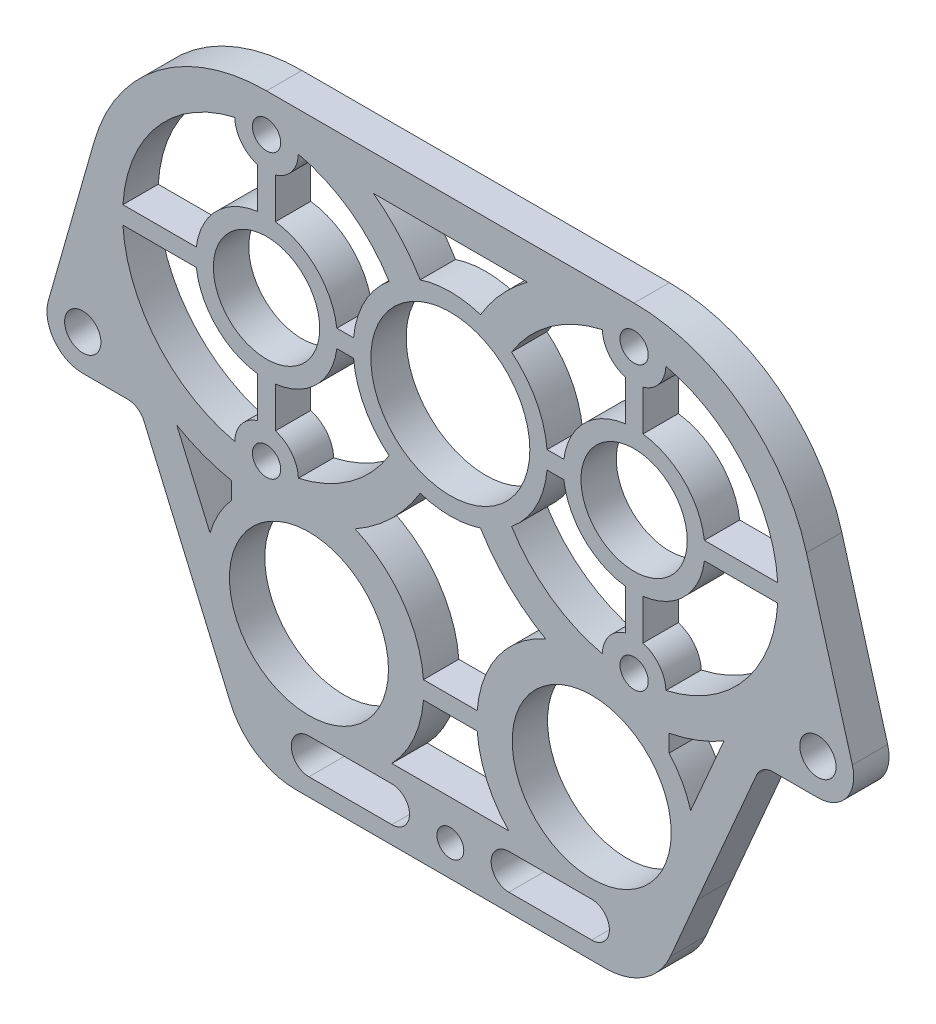
SolidWorks part; units mm, degrees
material "6061 Alloy"
ref_plane "Front Plane" through (0, 0, 0) normal (0, 0, 1) x (1, 0, 0)
ref_plane "Top Plane" through (0, 0, 0) normal (0, 1, 0) x (1, 0, 0)
ref_plane "Right Plane" through (0, 0, 0) normal (1, 0, 0) x (0, 0, -1)
sketch "Sketch1" plane through (0, 0, 0) normal (0, 0, 1) x (1, 0, 0)
  line L0 (-88.7296, -57.0475) -> (-96.9696, -85.9369)
  line L1 (-70.3836, -64.2939) -> (-83.566, -64.2939)
  line L2 (-59.3451, -45.9715) -> (-59.3451, -53.2554)
  line L3 (-59.3451, -85.7913) -> (-59.3451, -78.5074)
  line L4 (-56.1701, -45.9715) -> (-56.1701, -53.2554)
  line L5 (-45.1316, -64.2939) -> (-42.1278, -64.2939)
  line L6 (-56.1701, -85.7913) -> (-56.1701, -78.5074)
  line L7 (-70.3836, -67.4689) -> (-83.566, -67.4689)
  line L8 (-73.8894, -93.7574) -> (-67.9201, -107.5525)
  line L9 (-45.1316, -67.4689) -> (-42.1278, -67.4689)
  line L10 (-64.0572, -97.4665) -> (-64.0572, -100.5443)
  line L11 (-69.0893, -120.875) -> (-60.9774, -139.773)
  line L13 (-29.5612, -111.198) -> (-19.9139, -111.198)
  line L14 (-14.2297, -127.073) -> (-35.2455, -127.073)
  line L15 (-29.5612, -114.373) -> (-19.9139, -114.373)
  line L16 (-57.7576, -33.6742) -> (8.2824, -33.6742)
  line L17 (-10.9194, -40.0242) -> (-38.5558, -40.0242)
  line L18 (30.2994, -96.0869) -> (19.6141, -120.875)
  line L19 (-4.3436, -67.4689) -> (-7.3474, -67.4689)
  line L20 (41.3024, -94.1419) -> (33.2559, -94.1419)
  line L21 (20.9084, -67.4689) -> (34.0908, -67.4689)
  line L22 (6.6949, -85.7913) -> (6.6949, -78.5074)
  line L23 (-4.3436, -64.2939) -> (-7.3474, -64.2939)
  line L24 (6.6949, -45.9715) -> (6.6949, -53.2554)
  line L25 (9.8699, -85.7913) -> (9.8699, -78.5074)
  line L26 (9.8699, -45.9715) -> (9.8699, -53.2554)
  line L27 (20.9084, -64.2939) -> (34.0908, -64.2939)
  line L28 (39.2544, -57.0475) -> (47.4944, -85.9369)
  line L29 (-90.7776, -94.1419) -> (-82.7311, -94.1419)
  line L30 (-79.7746, -96.0869) -> (-69.0893, -120.875)
  line L31 (-60.9774, -139.773) -> (11.5022, -139.773)
  line L32 (19.6141, -120.875) -> (11.5022, -139.773)
  line L33 (24.4142, -93.7574) -> (18.4449, -107.5525)
  line L34 (-35.2455, -133.423) -> (-50.1376, -133.423) construction
  line L35 (-35.2455, -136.598) -> (-50.1376, -136.598)
  line L36 (-35.2455, -130.248) -> (-50.1376, -130.248)
  line L37 (0.6624, -133.423) -> (-14.2297, -133.423) construction
  line L38 (0.6624, -136.598) -> (-14.2297, -136.598)
  line L39 (0.6624, -130.248) -> (-14.2297, -130.248)
  line L40 (14.582, -97.4665) -> (14.582, -100.5443)
  circle A0 centre (-57.7576, -65.8814) radius 9.5504
  circle A1 centre (-57.7576, -40.4814) radius 2.54
  arc A2 (-41.8493, -93.8855) -> (-30.1579, -82.4814) centre (-57.7576, -65.8814) ccw
  circle A3 centre (-57.7576, -91.2814) radius 2.54
  circle A4 centre (-90.7776, -87.703) radius 3.2639
  arc A5 (-52.0455, -91.0998) -> (-56.1701, -85.7913) centre (-57.7576, -91.2814) ccw
  arc A6 (-52.0455, -91.0998) -> (-35.741, -79.4411) centre (-57.7576, -65.8814) ccw
  arc A7 (-52.0455, -40.663) -> (-56.1701, -45.9715) centre (-57.7576, -40.4814) cw
  arc A8 (-59.3451, -45.9715) -> (-63.4697, -40.663) centre (-57.7576, -40.4814) cw
  arc A9 (-56.1701, -78.5074) -> (-45.1316, -67.4689) centre (-57.7576, -65.8814) ccw
  arc A10 (-59.3451, -85.7913) -> (-63.4697, -91.0998) centre (-57.7576, -91.2814) ccw
  arc A11 (-83.566, -67.4689) -> (-63.4697, -91.0998) centre (-57.7576, -65.8814) ccw
  arc A12 (-59.3451, -53.2554) -> (-70.3836, -64.2939) centre (-57.7576, -65.8814) ccw
  circle A13 centre (-50.1376, -112.7855) radius 14.2875
  arc A14 (-70.3836, -67.4689) -> (-59.3451, -78.5074) centre (-57.7576, -65.8814) ccw
  arc A15 (-45.1316, -64.2939) -> (-56.1701, -53.2554) centre (-57.7576, -65.8814) ccw
  arc A16 (-63.4697, -40.663) -> (-83.566, -64.2939) centre (-57.7576, -65.8814) ccw
  arc A17 (-30.1579, -82.4814) -> (-19.3173, -82.4814) centre (-24.7376, -65.8814) ccw
  arc A18 (-64.0572, -100.5443) -> (-67.9201, -107.5525) centre (-50.1376, -112.7855) ccw
  arc A19 (39.1749, -56.7733) -> (39.2544, -57.0475) centre (8.2824, -65.8814) cw
  circle A20 centre (-24.7376, -65.8814) radius 14.2875
  arc A21 (-35.741, -52.3218) -> (-42.1278, -64.2939) centre (-24.7376, -65.8814) ccw
  arc A22 (-35.741, -52.3218) -> (-52.0455, -40.663) centre (-57.7576, -65.8814) ccw
  arc A23 (-42.1278, -67.4689) -> (-35.741, -79.4411) centre (-24.7376, -65.8814) ccw
  arc A24 (-30.1579, -49.2814) -> (-38.5558, -40.0242) centre (-57.7576, -65.8814) ccw
  arc A25 (-19.3173, -49.2814) -> (-30.1579, -49.2814) centre (-24.7376, -65.8814) ccw
  arc A26 (-29.5612, -111.198) -> (-41.8493, -93.8855) centre (-50.1376, -112.7855) ccw
  arc A27 (-35.2455, -127.073) -> (-29.5612, -114.373) centre (-50.1376, -112.7855) ccw
  arc A28 (-57.7576, -33.6742) -> (-88.6501, -56.7733) centre (-57.7576, -65.8814) ccw
  arc A29 (8.2824, -33.6742) -> (39.1749, -56.7733) centre (8.2824, -65.8814) cw
  arc A30 (-14.2297, -127.073) -> (-19.9139, -114.373) centre (0.6624, -112.7855) cw
  arc A31 (-19.9139, -111.198) -> (-7.6259, -93.8855) centre (0.6624, -112.7855) cw
  arc A32 (-19.3173, -49.2814) -> (-10.9194, -40.0242) centre (8.2824, -65.8814) cw
  arc A33 (-7.3474, -67.4689) -> (-13.7342, -79.4411) centre (-24.7376, -65.8814) cw
  arc A34 (-13.7342, -52.3218) -> (2.5703, -40.663) centre (8.2824, -65.8814) cw
  arc A35 (-13.7342, -52.3218) -> (-7.3474, -64.2939) centre (-24.7376, -65.8814) cw
  arc A36 (30.2994, -96.0869) -> (33.2559, -94.1419) centre (33.2559, -97.3614) cw
  arc A37 (47.4944, -85.9369) -> (41.3024, -94.1419) centre (41.3024, -87.703) cw
  arc A38 (13.9945, -40.663) -> (34.0908, -64.2939) centre (8.2824, -65.8814) cw
  arc A39 (-4.3436, -64.2939) -> (6.6949, -53.2554) centre (8.2824, -65.8814) cw
  arc A40 (20.9084, -67.4689) -> (9.8699, -78.5074) centre (8.2824, -65.8814) cw
  circle A41 centre (0.6624, -112.7855) radius 14.2875
  arc A42 (9.8699, -53.2554) -> (20.9084, -64.2939) centre (8.2824, -65.8814) cw
  arc A43 (34.0908, -67.4689) -> (13.9945, -91.0998) centre (8.2824, -65.8814) cw
  arc A44 (9.8699, -85.7913) -> (13.9945, -91.0998) centre (8.2824, -91.2814) cw
  arc A45 (6.6949, -78.5074) -> (-4.3436, -67.4689) centre (8.2824, -65.8814) cw
  arc A46 (9.8699, -45.9715) -> (13.9945, -40.663) centre (8.2824, -40.4814) ccw
  arc A47 (2.5703, -40.663) -> (6.6949, -45.9715) centre (8.2824, -40.4814) ccw
  arc A48 (2.5703, -91.0998) -> (-13.7342, -79.4411) centre (8.2824, -65.8814) cw
  arc A49 (2.5703, -91.0998) -> (6.6949, -85.7913) centre (8.2824, -91.2814) cw
  arc A50 (-96.9696, -85.9369) -> (-90.7776, -94.1419) centre (-90.7776, -87.703) ccw
  circle A51 centre (8.2824, -91.2814) radius 2.54
  arc A52 (-7.6259, -93.8855) -> (-19.3173, -82.4814) centre (8.2824, -65.8814) cw
  circle A53 centre (8.2824, -40.4814) radius 2.54
  circle A54 centre (8.2824, -65.8814) radius 9.5504
  arc A55 (-35.2455, -136.598) -> (-35.2455, -130.248) centre (-35.2455, -133.423) ccw
  circle A56 centre (-24.7376, -134.185) radius 2.413
  arc A57 (-50.1376, -130.248) -> (-50.1376, -136.598) centre (-50.1376, -133.423) ccw
  arc A58 (0.6624, -136.598) -> (0.6624, -130.248) centre (0.6624, -133.423) ccw
  arc A59 (-14.2297, -130.248) -> (-14.2297, -136.598) centre (-14.2297, -133.423) ccw
  arc A60 (-79.7746, -96.0869) -> (-82.7311, -94.1419) centre (-82.7311, -97.3614) ccw
  circle A61 centre (41.3024, -87.703) radius 3.2639
  arc A62 (14.582, -100.5443) -> (18.4449, -107.5525) centre (0.6624, -112.7855) cw
  arc A63 (24.4142, -93.7574) -> (14.582, -97.4665) centre (8.2824, -65.8814) cw
  arc A65 (-88.6501, -56.7733) -> (-88.7296, -57.0475) centre (-57.7576, -65.8814) ccw
  arc A66 (-73.8894, -93.7574) -> (-64.0572, -97.4665) centre (-57.7576, -65.8814) ccw
  point P3 (-24.7376, -65.8814)
  point P48 (-24.7376, -127.073)
  point P50 (-15.8172, -133.423)
  point P51 (-24.7376, -111.198)
  point P54 (-24.7376, -111.198)
  point P57 (-24.7376, -114.373)
  point P58 (-24.7376, -33.6742)
  point P104 (-24.7376, -40.0242)
  point P109 (-60.9774, -139.773)
  point P112 (-42.6916, -133.423)
  point P113 (11.5022, -139.773)
  point P118 (-6.7836, -133.423)
  dimension "D2" = 19.1008
  dimension "D4" = 5.08
  dimension "D8" = 25.4
  dimension "D9" = 3.175
  dimension "D10" = 11.43
  dimension "D11" = 33.02
  dimension "D12" = 46.9041
  dimension "D13" = 25.4
  dimension "D14" = 6.5278
  dimension "D15" = 1.5875
  dimension "D17" = 5.715
  dimension "D18" = 28.575
  dimension "D23" = 1.5875
  dimension "D27" = 6.4389
  dimension "D7" = 64.4144
  dimension "D28" = 34.925
  dimension "D29" = 25.4508
  dimension "D30" = 51.7144
  dimension "D5" = 5.08
  dimension "D16" = 5.715
  dimension "D25" = 28.575
  dimension "D26" = 3.2195
  dimension "D36" = 3.175
  dimension "D37" = 4.826
  dimension "D40" = 3.175
  dimension "D41" = 32.2072
  dimension "D6" = 25.4
  dimension "D19" = 3.175
  dimension "D20" = 1.5875
  dimension "D31" = 3.175
  dimension "D21" = 33.02
  dimension "D22" = 3.175
  dimension "D32" = 1.5875
  dimension "D33" = 28.2605
  dimension "D34" = 6.35
  dimension "D35" = 26.9875
  dimension "D38" = 5.588
  dimension "D39" = 0
  dimension "D45" = 66.04
extrude "Boss-Extrude1" add sketch "Sketch1" along normal blind 6.35 contours A0 region at (-86.9649, -57.4107, 0)
fillet "Fillet1" radius 12.7 2 edges at (-60.9774, -139.773, 3.175) (11.5022, -139.773, 3.175)
